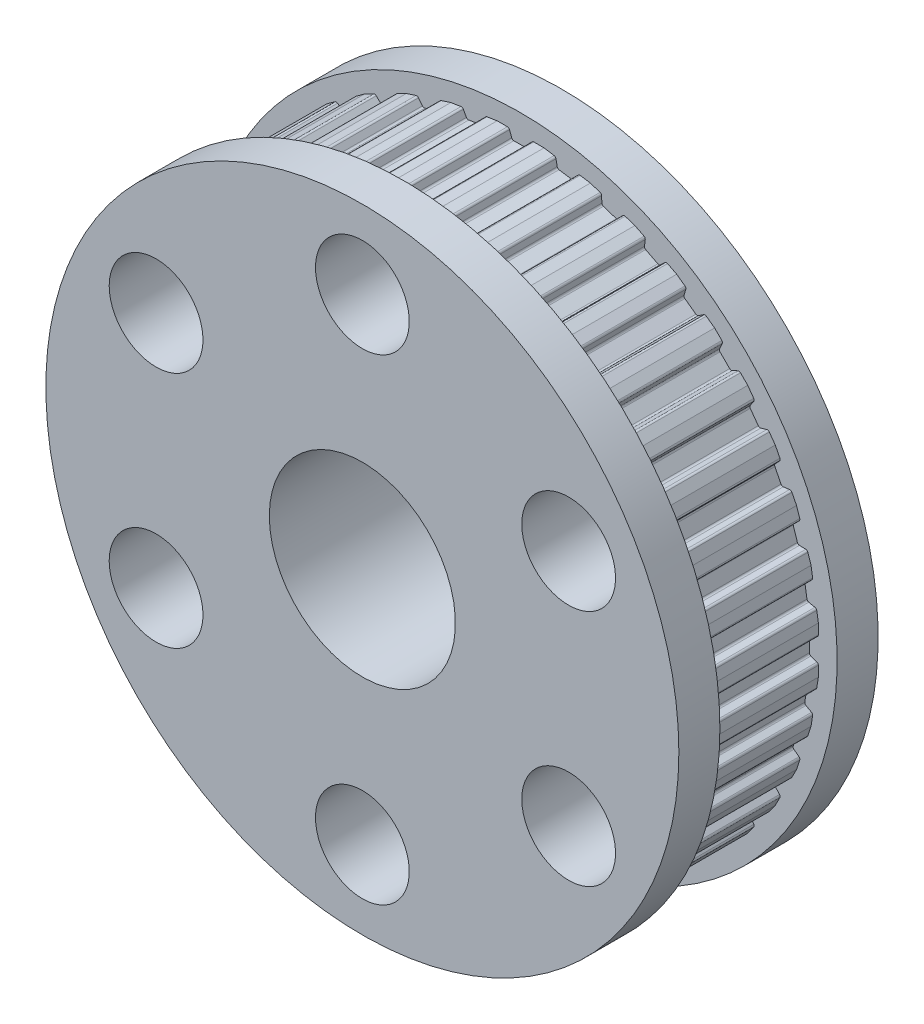
SolidWorks part; units mm, degrees
ref_plane "Front Plane" through (0, 0, 0) normal (0, 0, 1) x (1, 0, 0)
ref_plane "Top Plane" through (0, 0, 0) normal (0, 1, 0) x (1, 0, 0)
ref_plane "Right Plane" through (0, 0, 0) normal (1, 0, 0) x (0, 0, -1)
sketch "Sketch1" plane through (0, 0, 0) normal (0, 0, 1) x (1, 0, 0)
  line L0 (-50.7835, 0) -> (-50.3466, 0)
  line L5 (-50.2571, 0.0627) -> (-50.1641, 0.3183)
  line L6 (-50.0746, 0.381) -> (-49.4934, 0.381)
  line L7 (-49.784, 0.381) -> (-49.784, 0) construction
  line L8 (-49.3109, 0.0627) -> (-49.4039, 0.3183)
  line L39 (-51.2936, 0.1442) -> (-51.3455, 0.4113)
  line L40 (-50.2571, 0.0627) -> (-49.3109, 0.0627) construction
  line L56 (-49.2214, 0) -> (-48.7845, 0)
  line L60 (-51.9981, 0.5781) -> (-51.4241, 0.4872)
  line L61 (-52.2282, 0.2923) -> (-52.0963, 0.5302)
  line L62 (-52.7579, 0.3127) -> (-52.3264, 0.2444)
  line L63 (-51.215, 0.0683) -> (-50.7835, 0)
  line L64 (-53.2392, 0.535) -> (-53.2487, 0.8069)
  line L65 (-53.8671, 1.0737) -> (-53.3144, 0.8941)
  line L66 (-54.1391, 0.8274) -> (-53.9716, 1.0418)
  line L67 (-54.6591, 0.9304) -> (-54.2436, 0.7954)
  line L68 (-53.1734, 0.4477) -> (-52.7579, 0.3127)
  line L69 (-55.0997, 1.2253) -> (-55.0665, 1.4953)
  line L70 (-55.6356, 1.8556) -> (-55.1178, 1.5918)
  line L71 (-55.9428, 1.6549) -> (-55.7438, 1.8404)
  line L72 (-56.4403, 1.838) -> (-56.051, 1.6396)
  line L73 (-55.0484, 1.1288) -> (-54.6591, 0.9304)
  line L74 (-56.8293, 2.1981) -> (-56.7543, 2.4596)
  line L75 (-57.26, 2.9045) -> (-56.7898, 2.5629)
  line L76 (-57.5948, 2.7543) -> (-57.3693, 2.9064)
  line L77 (-58.0575, 3.013) -> (-57.7041, 2.7562)
  line L78 (-56.7937, 2.0948) -> (-56.4403, 1.838)
  line L79 (-58.3854, 3.4295) -> (-58.2704, 3.6761)
  line L80 (-58.7003, 4.1946) -> (-58.2894, 3.7837)
  line L81 (-59.0545, 4.0986) -> (-58.8079, 4.2136)
  line L82 (-59.471, 4.4265) -> (-59.1621, 4.1176)
  line L83 (-58.3664, 3.3219) -> (-58.0575, 3.013)
  line L84 (-59.7297, 4.8892) -> (-59.5776, 5.1147)
  line L85 (-59.9211, 5.6942) -> (-59.5795, 5.224)
  line L86 (-60.2859, 5.6547) -> (-60.0244, 5.7297)
  line L87 (-60.646, 6.0437) -> (-60.3892, 5.6903)
  line L88 (-59.7278, 4.7799) -> (-59.471, 4.4265)
  line L89 (-60.8291, 6.5412) -> (-60.6436, 6.7402)
  line L90 (-60.8922, 7.3662) -> (-60.6284, 6.8484)
  line L91 (-61.2587, 7.3843) -> (-60.9887, 7.4175)
  line L92 (-61.5536, 7.8249) -> (-61.3552, 7.4356)
  line L93 (-60.8444, 6.433) -> (-60.646, 6.0437)
  line L94 (-61.6566, 8.3449) -> (-61.4422, 8.5124)
  line L95 (-61.5899, 9.1696) -> (-61.4103, 8.6169)
  line L96 (-61.949, 9.2448) -> (-61.6771, 9.2353)
  line L97 (-62.1713, 9.7261) -> (-62.0363, 9.3106)
  line L98 (-61.6886, 8.2404) -> (-61.5536, 7.8249)
  line L99 (-62.1917, 10.2558) -> (-61.9538, 10.3877)
  line L100 (-61.9968, 11.0599) -> (-61.9059, 10.4859)
  line L101 (-62.3398, 11.1904) -> (-62.0727, 11.1385)
  line L102 (-62.484, 11.7005) -> (-62.4157, 11.269)
  line L103 (-62.2396, 10.1576) -> (-62.1713, 9.7261)
  line L104 (-62.4213, 12.2269) -> (-62.1657, 12.3199)
  line L105 (-62.103, 12.9906) -> (-62.103, 12.4094)
  line L106 (-62.4213, 13.1731) -> (-62.1657, 13.0801)
  line L107 (-62.484, 13.6995) -> (-62.484, 13.2626)
  line L108 (-62.484, 12.1374) -> (-62.484, 11.7005)
  line L109 (-62.3398, 14.2096) -> (-62.0727, 14.2615)
  line L110 (-61.9059, 14.9141) -> (-61.9968, 14.3401)
  line L111 (-62.1917, 15.1442) -> (-61.9538, 15.0123)
  line L112 (-62.1713, 15.6739) -> (-62.2396, 15.2424)
  line L113 (-62.4157, 14.131) -> (-62.484, 13.6995)
  line L114 (-61.949, 16.1552) -> (-61.6771, 16.1647)
  line L115 (-61.4103, 16.7831) -> (-61.5899, 16.2304)
  line L116 (-61.6566, 17.0551) -> (-61.4422, 16.8876)
  line L117 (-61.5536, 17.5751) -> (-61.6886, 17.1596)
  line L118 (-62.0363, 16.0894) -> (-62.1713, 15.6739)
  line L119 (-61.2587, 18.0157) -> (-60.9887, 17.9825)
  line L120 (-60.6284, 18.5516) -> (-60.8922, 18.0338)
  line L121 (-60.8291, 18.8588) -> (-60.6436, 18.6598)
  line L122 (-60.646, 19.3563) -> (-60.8444, 18.967)
  line L123 (-61.3552, 17.9644) -> (-61.5536, 17.5751)
  line L124 (-60.2859, 19.7453) -> (-60.0244, 19.6703)
  line L125 (-59.5795, 20.176) -> (-59.9211, 19.7058)
  line L126 (-59.7297, 20.5108) -> (-59.5776, 20.2853)
  line L127 (-59.471, 20.9735) -> (-59.7278, 20.6201)
  line L128 (-60.3892, 19.7097) -> (-60.646, 19.3563)
  line L129 (-59.0545, 21.3014) -> (-58.8079, 21.1864)
  line L130 (-58.2894, 21.6163) -> (-58.7003, 21.2054)
  line L131 (-58.3854, 21.9705) -> (-58.2704, 21.7239)
  line L132 (-58.0575, 22.387) -> (-58.3664, 22.0781)
  line L133 (-59.1621, 21.2824) -> (-59.471, 20.9735)
  line L134 (-57.5948, 22.6457) -> (-57.3693, 22.4936)
  line L135 (-56.7898, 22.8371) -> (-57.26, 22.4955)
  line L136 (-56.8293, 23.2019) -> (-56.7543, 22.9404)
  line L137 (-56.4403, 23.562) -> (-56.7937, 23.3052)
  line L138 (-57.7041, 22.6438) -> (-58.0575, 22.387)
  line L139 (-55.9428, 23.7451) -> (-55.7438, 23.5596)
  line L140 (-55.1178, 23.8082) -> (-55.6356, 23.5444)
  line L141 (-55.0997, 24.1747) -> (-55.0665, 23.9047)
  line L142 (-54.6591, 24.4696) -> (-55.0484, 24.2712)
  line L143 (-56.051, 23.7604) -> (-56.4403, 23.562)
  line L144 (-54.1391, 24.5726) -> (-53.9716, 24.3582)
  line L145 (-53.3144, 24.5059) -> (-53.8671, 24.3263)
  line L146 (-53.2392, 24.865) -> (-53.2487, 24.5931)
  line L147 (-52.7579, 25.0873) -> (-53.1734, 24.9523)
  line L148 (-54.2436, 24.6046) -> (-54.6591, 24.4696)
  line L149 (-52.2282, 25.1077) -> (-52.0963, 24.8698)
  line L150 (-51.4241, 24.9128) -> (-51.9981, 24.8219)
  line L151 (-51.2936, 25.2558) -> (-51.3455, 24.9887)
  line L152 (-50.7835, 25.4) -> (-51.215, 25.3317)
  line L153 (-52.3264, 25.1556) -> (-52.7579, 25.0873)
  line L154 (-50.2571, 25.3373) -> (-50.1641, 25.0817)
  line L155 (-49.4934, 25.019) -> (-50.0746, 25.019)
  line L156 (-49.3109, 25.3373) -> (-49.4039, 25.0817)
  line L157 (-48.7845, 25.4) -> (-49.2214, 25.4)
  line L158 (-50.3466, 25.4) -> (-50.7835, 25.4)
  line L159 (-48.2744, 25.2558) -> (-48.2225, 24.9887)
  line L160 (-47.5699, 24.8219) -> (-48.1439, 24.9128)
  line L161 (-47.3398, 25.1077) -> (-47.4717, 24.8698)
  line L162 (-46.8101, 25.0873) -> (-47.2416, 25.1556)
  line L163 (-48.353, 25.3317) -> (-48.7845, 25.4)
  line L164 (-46.3288, 24.865) -> (-46.3193, 24.5931)
  line L165 (-45.7009, 24.3263) -> (-46.2536, 24.5059)
  line L166 (-45.4289, 24.5726) -> (-45.5964, 24.3582)
  line L167 (-44.9089, 24.4696) -> (-45.3244, 24.6046)
  line L168 (-46.3946, 24.9523) -> (-46.8101, 25.0873)
  line L169 (-44.4683, 24.1747) -> (-44.5015, 23.9047)
  line L170 (-43.9324, 23.5444) -> (-44.4502, 23.8082)
  line L171 (-43.6252, 23.7451) -> (-43.8242, 23.5596)
  line L172 (-43.1277, 23.562) -> (-43.517, 23.7604)
  line L173 (-44.5196, 24.2712) -> (-44.9089, 24.4696)
  line L174 (-42.7387, 23.2019) -> (-42.8137, 22.9404)
  line L175 (-42.308, 22.4955) -> (-42.7782, 22.8371)
  line L176 (-41.9732, 22.6457) -> (-42.1987, 22.4936)
  line L177 (-41.5105, 22.387) -> (-41.8639, 22.6438)
  line L178 (-42.7743, 23.3052) -> (-43.1277, 23.562)
  line L179 (-41.1826, 21.9705) -> (-41.2976, 21.7239)
  line L180 (-40.8677, 21.2054) -> (-41.2786, 21.6163)
  line L181 (-40.5135, 21.3014) -> (-40.7601, 21.1864)
  line L182 (-40.097, 20.9735) -> (-40.4059, 21.2824)
  line L183 (-41.2016, 22.0781) -> (-41.5105, 22.387)
  line L184 (-39.8383, 20.5108) -> (-39.9904, 20.2853)
  line L185 (-39.6469, 19.7058) -> (-39.9885, 20.176)
  line L186 (-39.2821, 19.7453) -> (-39.5436, 19.6703)
  line L187 (-38.922, 19.3563) -> (-39.1788, 19.7097)
  line L188 (-39.8402, 20.6201) -> (-40.097, 20.9735)
  line L189 (-38.7389, 18.8588) -> (-38.9244, 18.6598)
  line L190 (-38.6758, 18.0338) -> (-38.9396, 18.5516)
  line L191 (-38.3093, 18.0157) -> (-38.5793, 17.9825)
  line L192 (-38.0144, 17.5751) -> (-38.2128, 17.9644)
  line L193 (-38.7236, 18.967) -> (-38.922, 19.3563)
  line L194 (-37.9114, 17.0551) -> (-38.1258, 16.8876)
  line L195 (-37.9781, 16.2304) -> (-38.1577, 16.7831)
  line L196 (-37.619, 16.1552) -> (-37.8909, 16.1647)
  line L197 (-37.3967, 15.6739) -> (-37.5317, 16.0894)
  line L198 (-37.8794, 17.1596) -> (-38.0144, 17.5751)
  line L199 (-37.3763, 15.1442) -> (-37.6142, 15.0123)
  line L200 (-37.5712, 14.3401) -> (-37.6621, 14.9141)
  line L201 (-37.2282, 14.2096) -> (-37.4953, 14.2615)
  line L202 (-37.084, 13.6995) -> (-37.1523, 14.131)
  line L203 (-37.3284, 15.2424) -> (-37.3967, 15.6739)
  line L204 (-37.1467, 13.1731) -> (-37.4023, 13.0801)
  line L205 (-37.465, 12.4094) -> (-37.465, 12.9906)
  line L206 (-37.1467, 12.2269) -> (-37.4023, 12.3199)
  line L207 (-37.084, 11.7005) -> (-37.084, 12.1374)
  line L208 (-37.084, 13.2626) -> (-37.084, 13.6995)
  line L209 (-37.2282, 11.1904) -> (-37.4953, 11.1385)
  line L210 (-37.6621, 10.4859) -> (-37.5712, 11.0599)
  line L211 (-37.3763, 10.2558) -> (-37.6142, 10.3877)
  line L212 (-37.3967, 9.7261) -> (-37.3284, 10.1576)
  line L213 (-37.1523, 11.269) -> (-37.084, 11.7005)
  line L214 (-37.619, 9.2448) -> (-37.8909, 9.2353)
  line L215 (-38.1577, 8.6169) -> (-37.9781, 9.1696)
  line L216 (-37.9114, 8.3449) -> (-38.1258, 8.5124)
  line L217 (-38.0144, 7.8249) -> (-37.8794, 8.2404)
  line L218 (-37.5317, 9.3106) -> (-37.3967, 9.7261)
  line L219 (-38.3093, 7.3843) -> (-38.5793, 7.4175)
  line L220 (-38.9396, 6.8484) -> (-38.6758, 7.3662)
  line L221 (-38.7389, 6.5412) -> (-38.9244, 6.7402)
  line L222 (-38.922, 6.0437) -> (-38.7236, 6.433)
  line L223 (-38.2128, 7.4356) -> (-38.0144, 7.8249)
  line L224 (-39.2821, 5.6547) -> (-39.5436, 5.7297)
  line L225 (-39.9885, 5.224) -> (-39.6469, 5.6942)
  line L226 (-39.8383, 4.8892) -> (-39.9904, 5.1147)
  line L227 (-40.097, 4.4265) -> (-39.8402, 4.7799)
  line L228 (-39.1788, 5.6903) -> (-38.922, 6.0437)
  line L229 (-40.5135, 4.0986) -> (-40.7601, 4.2136)
  line L230 (-41.2786, 3.7837) -> (-40.8677, 4.1946)
  line L231 (-41.1826, 3.4295) -> (-41.2976, 3.6761)
  line L232 (-41.5105, 3.013) -> (-41.2016, 3.3219)
  line L233 (-40.4059, 4.1176) -> (-40.097, 4.4265)
  line L234 (-41.9732, 2.7543) -> (-42.1987, 2.9064)
  line L235 (-42.7782, 2.5629) -> (-42.308, 2.9045)
  line L236 (-42.7387, 2.1981) -> (-42.8137, 2.4596)
  line L237 (-43.1277, 1.838) -> (-42.7743, 2.0948)
  line L238 (-41.8639, 2.7562) -> (-41.5105, 3.013)
  line L239 (-43.6252, 1.6549) -> (-43.8242, 1.8404)
  line L240 (-44.4502, 1.5918) -> (-43.9324, 1.8556)
  line L241 (-44.4683, 1.2253) -> (-44.5015, 1.4953)
  line L242 (-44.9089, 0.9304) -> (-44.5196, 1.1288)
  line L243 (-43.517, 1.6396) -> (-43.1277, 1.838)
  line L244 (-45.4289, 0.8274) -> (-45.5964, 1.0418)
  line L245 (-46.2536, 0.8941) -> (-45.7009, 1.0737)
  line L246 (-46.3288, 0.535) -> (-46.3193, 0.8069)
  line L247 (-46.8101, 0.3127) -> (-46.3946, 0.4477)
  line L248 (-45.3244, 0.7954) -> (-44.9089, 0.9304)
  line L249 (-47.3398, 0.2923) -> (-47.4717, 0.5302)
  line L250 (-48.1439, 0.4872) -> (-47.5699, 0.5781)
  line L251 (-48.2744, 0.1442) -> (-48.2225, 0.4113)
  line L252 (-48.7845, 0) -> (-48.353, 0.0683)
  line L253 (-47.2416, 0.2444) -> (-46.8101, 0.3127)
  arc A0 (-50.3466, 0) -> (-50.2571, 0.0627) centre (-50.3466, 0.0952) ccw
  arc A1 (-50.1641, 0.3183) -> (-50.0746, 0.381) centre (-50.0746, 0.2857) cw
  arc A2 (-49.4039, 0.3183) -> (-49.4934, 0.381) centre (-49.4934, 0.2857) ccw
  arc A3 (-49.2214, 0) -> (-49.3109, 0.0627) centre (-49.2214, 0.0952) cw
  arc A4 (-51.215, 0.0683) -> (-51.2936, 0.1442) centre (-51.2001, 0.1624) cw
  arc A5 (-51.3455, 0.4113) -> (-51.4241, 0.4872) centre (-51.439, 0.3931) ccw
  arc A6 (-52.0963, 0.5302) -> (-51.9981, 0.5781) centre (-52.013, 0.484) cw
  arc A7 (-52.3264, 0.2444) -> (-52.2282, 0.2923) centre (-52.3115, 0.3385) ccw
  arc A8 (-53.1734, 0.4477) -> (-53.2392, 0.535) centre (-53.144, 0.5383) cw
  arc A9 (-53.2487, 0.8069) -> (-53.3144, 0.8941) centre (-53.3439, 0.8036) ccw
  arc A10 (-53.9716, 1.0418) -> (-53.8671, 1.0737) centre (-53.8966, 0.9831) cw
  arc A11 (-54.2436, 0.7954) -> (-54.1391, 0.8274) centre (-54.2142, 0.886) ccw
  arc A12 (-55.0484, 1.1288) -> (-55.0997, 1.2253) centre (-55.0051, 1.2137) cw
  arc A13 (-55.0665, 1.4953) -> (-55.1178, 1.5918) centre (-55.1611, 1.5069) ccw
  arc A14 (-55.7438, 1.8404) -> (-55.6356, 1.8556) centre (-55.6789, 1.7707) cw
  arc A15 (-56.051, 1.6396) -> (-55.9428, 1.6549) centre (-56.0077, 1.7245) ccw
  arc A16 (-56.7937, 2.0948) -> (-56.8293, 2.1981) centre (-56.7377, 2.1718) cw
  arc A17 (-56.7543, 2.4596) -> (-56.7898, 2.5629) centre (-56.8458, 2.4859) ccw
  arc A18 (-57.3693, 2.9064) -> (-57.26, 2.9045) centre (-57.316, 2.8275) cw
  arc A19 (-57.7041, 2.7562) -> (-57.5948, 2.7543) centre (-57.6481, 2.8333) ccw
  arc A20 (-58.3664, 3.3219) -> (-58.3854, 3.4295) centre (-58.2991, 3.3893) cw
  arc A21 (-58.2704, 3.6761) -> (-58.2894, 3.7837) centre (-58.3567, 3.7163) ccw
  arc A22 (-58.8079, 4.2136) -> (-58.7003, 4.1946) centre (-58.7677, 4.1273) cw
  arc A23 (-59.1621, 4.1176) -> (-59.0545, 4.0986) centre (-59.0947, 4.1849) ccw
  arc A24 (-59.7278, 4.7799) -> (-59.7297, 4.8892) centre (-59.6507, 4.8359) cw
  arc A25 (-59.5776, 5.1147) -> (-59.5795, 5.224) centre (-59.6565, 5.168) ccw
  arc A26 (-60.0244, 5.7297) -> (-59.9211, 5.6942) centre (-59.9981, 5.6382) cw
  arc A27 (-60.3892, 5.6903) -> (-60.2859, 5.6547) centre (-60.3122, 5.7463) ccw
  arc A28 (-60.8444, 6.433) -> (-60.8291, 6.5412) centre (-60.7595, 6.4763) cw
  arc A29 (-60.6436, 6.7402) -> (-60.6284, 6.8484) centre (-60.7133, 6.8051) ccw
  arc A30 (-60.9887, 7.4175) -> (-60.8922, 7.3662) centre (-60.9771, 7.3229) cw
  arc A31 (-61.3552, 7.4356) -> (-61.2587, 7.3843) centre (-61.2703, 7.4789) ccw
  arc A32 (-61.6886, 8.2404) -> (-61.6566, 8.3449) centre (-61.598, 8.2698) cw
  arc A33 (-61.4422, 8.5124) -> (-61.4103, 8.6169) centre (-61.5009, 8.5874) ccw
  arc A34 (-61.6771, 9.2353) -> (-61.5899, 9.1696) centre (-61.6804, 9.1401) cw
  arc A35 (-62.0363, 9.3106) -> (-61.949, 9.2448) centre (-61.9457, 9.34) ccw
  arc A36 (-62.2396, 10.1576) -> (-62.1917, 10.2558) centre (-62.1455, 10.1725) cw
  arc A37 (-61.9538, 10.3877) -> (-61.9059, 10.4859) centre (-62, 10.471) ccw
  arc A38 (-62.0727, 11.1385) -> (-61.9968, 11.0599) centre (-62.0909, 11.045) cw
  arc A39 (-62.4157, 11.269) -> (-62.3398, 11.1904) centre (-62.3216, 11.2839) ccw
  arc A40 (-62.484, 12.1374) -> (-62.4213, 12.2269) centre (-62.3888, 12.1374) cw
  arc A41 (-62.1657, 12.3199) -> (-62.103, 12.4094) centre (-62.1983, 12.4094) ccw
  arc A42 (-62.1657, 13.0801) -> (-62.103, 12.9906) centre (-62.1983, 12.9906) cw
  arc A43 (-62.484, 13.2626) -> (-62.4213, 13.1731) centre (-62.3888, 13.2626) ccw
  arc A44 (-62.4157, 14.131) -> (-62.3398, 14.2096) centre (-62.3216, 14.1161) cw
  arc A45 (-62.0727, 14.2615) -> (-61.9968, 14.3401) centre (-62.0909, 14.355) ccw
  arc A46 (-61.9538, 15.0123) -> (-61.9059, 14.9141) centre (-62, 14.929) cw
  arc A47 (-62.2396, 15.2424) -> (-62.1917, 15.1442) centre (-62.1455, 15.2275) ccw
  arc A48 (-62.0363, 16.0894) -> (-61.949, 16.1552) centre (-61.9457, 16.06) cw
  arc A49 (-61.6771, 16.1647) -> (-61.5899, 16.2304) centre (-61.6804, 16.2599) ccw
  arc A50 (-61.4422, 16.8876) -> (-61.4103, 16.7831) centre (-61.5009, 16.8126) cw
  arc A51 (-61.6886, 17.1596) -> (-61.6566, 17.0551) centre (-61.598, 17.1302) ccw
  arc A52 (-61.3552, 17.9644) -> (-61.2587, 18.0157) centre (-61.2703, 17.9211) cw
  arc A53 (-60.9887, 17.9825) -> (-60.8922, 18.0338) centre (-60.9771, 18.0771) ccw
  arc A54 (-60.6436, 18.6598) -> (-60.6284, 18.5516) centre (-60.7133, 18.5949) cw
  arc A55 (-60.8444, 18.967) -> (-60.8291, 18.8588) centre (-60.7595, 18.9237) ccw
  arc A56 (-60.3892, 19.7097) -> (-60.2859, 19.7453) centre (-60.3122, 19.6537) cw
  arc A57 (-60.0244, 19.6703) -> (-59.9211, 19.7058) centre (-59.9981, 19.7618) ccw
  arc A58 (-59.5776, 20.2853) -> (-59.5795, 20.176) centre (-59.6565, 20.232) cw
  arc A59 (-59.7278, 20.6201) -> (-59.7297, 20.5108) centre (-59.6507, 20.5641) ccw
  arc A60 (-59.1621, 21.2824) -> (-59.0545, 21.3014) centre (-59.0947, 21.2151) cw
  arc A61 (-58.8079, 21.1864) -> (-58.7003, 21.2054) centre (-58.7677, 21.2727) ccw
  arc A62 (-58.2704, 21.7239) -> (-58.2894, 21.6163) centre (-58.3567, 21.6837) cw
  arc A63 (-58.3664, 22.0781) -> (-58.3854, 21.9705) centre (-58.2991, 22.0107) ccw
  arc A64 (-57.7041, 22.6438) -> (-57.5948, 22.6457) centre (-57.6481, 22.5667) cw
  arc A65 (-57.3693, 22.4936) -> (-57.26, 22.4955) centre (-57.316, 22.5725) ccw
  arc A66 (-56.7543, 22.9404) -> (-56.7898, 22.8371) centre (-56.8458, 22.9141) cw
  arc A67 (-56.7937, 23.3052) -> (-56.8293, 23.2019) centre (-56.7377, 23.2282) ccw
  arc A68 (-56.051, 23.7604) -> (-55.9428, 23.7451) centre (-56.0077, 23.6755) cw
  arc A69 (-55.7438, 23.5596) -> (-55.6356, 23.5444) centre (-55.6789, 23.6293) ccw
  arc A70 (-55.0665, 23.9047) -> (-55.1178, 23.8082) centre (-55.1611, 23.8931) cw
  arc A71 (-55.0484, 24.2712) -> (-55.0997, 24.1747) centre (-55.0051, 24.1863) ccw
  arc A72 (-54.2436, 24.6046) -> (-54.1391, 24.5726) centre (-54.2142, 24.514) cw
  arc A73 (-53.9716, 24.3582) -> (-53.8671, 24.3263) centre (-53.8966, 24.4169) ccw
  arc A74 (-53.2487, 24.5931) -> (-53.3144, 24.5059) centre (-53.3439, 24.5964) cw
  arc A75 (-53.1734, 24.9523) -> (-53.2392, 24.865) centre (-53.144, 24.8617) ccw
  arc A76 (-52.3264, 25.1556) -> (-52.2282, 25.1077) centre (-52.3115, 25.0615) cw
  arc A77 (-52.0963, 24.8698) -> (-51.9981, 24.8219) centre (-52.013, 24.916) ccw
  arc A78 (-51.3455, 24.9887) -> (-51.4241, 24.9128) centre (-51.439, 25.0069) cw
  arc A79 (-51.215, 25.3317) -> (-51.2936, 25.2558) centre (-51.2001, 25.2376) ccw
  arc A80 (-50.3466, 25.4) -> (-50.2571, 25.3373) centre (-50.3466, 25.3048) cw
  arc A81 (-50.1641, 25.0817) -> (-50.0746, 25.019) centre (-50.0746, 25.1143) ccw
  arc A82 (-49.4039, 25.0817) -> (-49.4934, 25.019) centre (-49.4934, 25.1143) cw
  arc A83 (-49.2214, 25.4) -> (-49.3109, 25.3373) centre (-49.2214, 25.3048) ccw
  arc A84 (-48.353, 25.3317) -> (-48.2744, 25.2558) centre (-48.3679, 25.2376) cw
  arc A85 (-48.2225, 24.9887) -> (-48.1439, 24.9128) centre (-48.129, 25.0069) ccw
  arc A86 (-47.4717, 24.8698) -> (-47.5699, 24.8219) centre (-47.555, 24.916) cw
  arc A87 (-47.2416, 25.1556) -> (-47.3398, 25.1077) centre (-47.2565, 25.0615) ccw
  arc A88 (-46.3946, 24.9523) -> (-46.3288, 24.865) centre (-46.424, 24.8617) cw
  arc A89 (-46.3193, 24.5931) -> (-46.2536, 24.5059) centre (-46.2241, 24.5964) ccw
  arc A90 (-45.5964, 24.3582) -> (-45.7009, 24.3263) centre (-45.6714, 24.4169) cw
  arc A91 (-45.3244, 24.6046) -> (-45.4289, 24.5726) centre (-45.3538, 24.514) ccw
  arc A92 (-44.5196, 24.2712) -> (-44.4683, 24.1747) centre (-44.5629, 24.1863) cw
  arc A93 (-44.5015, 23.9047) -> (-44.4502, 23.8082) centre (-44.4069, 23.8931) ccw
  arc A94 (-43.8242, 23.5596) -> (-43.9324, 23.5444) centre (-43.8891, 23.6293) cw
  arc A95 (-43.517, 23.7604) -> (-43.6252, 23.7451) centre (-43.5603, 23.6755) ccw
  arc A96 (-42.7743, 23.3052) -> (-42.7387, 23.2019) centre (-42.8303, 23.2282) cw
  arc A97 (-42.8137, 22.9404) -> (-42.7782, 22.8371) centre (-42.7222, 22.9141) ccw
  arc A98 (-42.1987, 22.4936) -> (-42.308, 22.4955) centre (-42.252, 22.5725) cw
  arc A99 (-41.8639, 22.6438) -> (-41.9732, 22.6457) centre (-41.9199, 22.5667) ccw
  arc A100 (-41.2016, 22.0781) -> (-41.1826, 21.9705) centre (-41.2689, 22.0107) cw
  arc A101 (-41.2976, 21.7239) -> (-41.2786, 21.6163) centre (-41.2113, 21.6837) ccw
  arc A102 (-40.7601, 21.1864) -> (-40.8677, 21.2054) centre (-40.8003, 21.2727) cw
  arc A103 (-40.4059, 21.2824) -> (-40.5135, 21.3014) centre (-40.4733, 21.2151) ccw
  arc A104 (-39.8402, 20.6201) -> (-39.8383, 20.5108) centre (-39.9173, 20.5641) cw
  arc A105 (-39.9904, 20.2853) -> (-39.9885, 20.176) centre (-39.9115, 20.232) ccw
  arc A106 (-39.5436, 19.6703) -> (-39.6469, 19.7058) centre (-39.5699, 19.7618) cw
  arc A107 (-39.1788, 19.7097) -> (-39.2821, 19.7453) centre (-39.2558, 19.6537) ccw
  arc A108 (-38.7236, 18.967) -> (-38.7389, 18.8588) centre (-38.8085, 18.9237) cw
  arc A109 (-38.9244, 18.6598) -> (-38.9396, 18.5516) centre (-38.8547, 18.5949) ccw
  arc A110 (-38.5793, 17.9825) -> (-38.6758, 18.0338) centre (-38.5909, 18.0771) cw
  arc A111 (-38.2128, 17.9644) -> (-38.3093, 18.0157) centre (-38.2977, 17.9211) ccw
  arc A112 (-37.8794, 17.1596) -> (-37.9114, 17.0551) centre (-37.97, 17.1302) cw
  arc A113 (-38.1258, 16.8876) -> (-38.1577, 16.7831) centre (-38.0671, 16.8126) ccw
  arc A114 (-37.8909, 16.1647) -> (-37.9781, 16.2304) centre (-37.8876, 16.2599) cw
  arc A115 (-37.5317, 16.0894) -> (-37.619, 16.1552) centre (-37.6223, 16.06) ccw
  arc A116 (-37.3284, 15.2424) -> (-37.3763, 15.1442) centre (-37.4225, 15.2275) cw
  arc A117 (-37.6142, 15.0123) -> (-37.6621, 14.9141) centre (-37.568, 14.929) ccw
  arc A118 (-37.4953, 14.2615) -> (-37.5712, 14.3401) centre (-37.4771, 14.355) cw
  arc A119 (-37.1523, 14.131) -> (-37.2282, 14.2096) centre (-37.2464, 14.1161) ccw
  arc A120 (-37.084, 13.2626) -> (-37.1467, 13.1731) centre (-37.1792, 13.2626) cw
  arc A121 (-37.4023, 13.0801) -> (-37.465, 12.9906) centre (-37.3697, 12.9906) ccw
  arc A122 (-37.4023, 12.3199) -> (-37.465, 12.4094) centre (-37.3698, 12.4094) cw
  arc A123 (-37.084, 12.1374) -> (-37.1467, 12.2269) centre (-37.1792, 12.1374) ccw
  arc A124 (-37.1523, 11.269) -> (-37.2282, 11.1904) centre (-37.2464, 11.2839) cw
  arc A125 (-37.4953, 11.1385) -> (-37.5712, 11.0599) centre (-37.4771, 11.045) ccw
  arc A126 (-37.6142, 10.3877) -> (-37.6621, 10.4859) centre (-37.568, 10.471) cw
  arc A127 (-37.3284, 10.1576) -> (-37.3763, 10.2558) centre (-37.4225, 10.1725) ccw
  arc A128 (-37.5317, 9.3106) -> (-37.619, 9.2448) centre (-37.6223, 9.34) cw
  arc A129 (-37.8909, 9.2353) -> (-37.9781, 9.1696) centre (-37.8876, 9.1401) ccw
  arc A130 (-38.1258, 8.5124) -> (-38.1577, 8.6169) centre (-38.0671, 8.5874) cw
  arc A131 (-37.8794, 8.2404) -> (-37.9114, 8.3449) centre (-37.97, 8.2698) ccw
  arc A132 (-38.2128, 7.4356) -> (-38.3093, 7.3843) centre (-38.2977, 7.4789) cw
  arc A133 (-38.5793, 7.4175) -> (-38.6758, 7.3662) centre (-38.5909, 7.3229) ccw
  arc A134 (-38.9244, 6.7402) -> (-38.9396, 6.8484) centre (-38.8547, 6.8051) cw
  arc A135 (-38.7236, 6.433) -> (-38.7389, 6.5412) centre (-38.8085, 6.4763) ccw
  arc A136 (-39.1788, 5.6903) -> (-39.2821, 5.6547) centre (-39.2558, 5.7463) cw
  arc A137 (-39.5436, 5.7297) -> (-39.6469, 5.6942) centre (-39.5699, 5.6382) ccw
  arc A138 (-39.9904, 5.1147) -> (-39.9885, 5.224) centre (-39.9115, 5.168) cw
  arc A139 (-39.8402, 4.7799) -> (-39.8383, 4.8892) centre (-39.9173, 4.8359) ccw
  arc A140 (-40.4059, 4.1176) -> (-40.5135, 4.0986) centre (-40.4733, 4.1849) cw
  arc A141 (-40.7601, 4.2136) -> (-40.8677, 4.1946) centre (-40.8003, 4.1273) ccw
  arc A142 (-41.2976, 3.6761) -> (-41.2786, 3.7837) centre (-41.2113, 3.7163) cw
  arc A143 (-41.2016, 3.3219) -> (-41.1826, 3.4295) centre (-41.2689, 3.3893) ccw
  arc A144 (-41.8639, 2.7562) -> (-41.9732, 2.7543) centre (-41.9199, 2.8333) cw
  arc A145 (-42.1987, 2.9064) -> (-42.308, 2.9045) centre (-42.252, 2.8275) ccw
  arc A146 (-42.8137, 2.4596) -> (-42.7782, 2.5629) centre (-42.7222, 2.4859) cw
  arc A147 (-42.7743, 2.0948) -> (-42.7387, 2.1981) centre (-42.8303, 2.1718) ccw
  arc A148 (-43.517, 1.6396) -> (-43.6252, 1.6549) centre (-43.5603, 1.7245) cw
  arc A149 (-43.8242, 1.8404) -> (-43.9324, 1.8556) centre (-43.8891, 1.7707) ccw
  arc A150 (-44.5015, 1.4953) -> (-44.4502, 1.5918) centre (-44.4069, 1.5069) cw
  arc A151 (-44.5196, 1.1288) -> (-44.4683, 1.2253) centre (-44.5629, 1.2137) ccw
  arc A152 (-45.3244, 0.7954) -> (-45.4289, 0.8274) centre (-45.3538, 0.886) cw
  arc A153 (-45.5964, 1.0418) -> (-45.7009, 1.0737) centre (-45.6714, 0.9831) ccw
  arc A154 (-46.3193, 0.8069) -> (-46.2536, 0.8941) centre (-46.2241, 0.8036) cw
  arc A155 (-46.3946, 0.4477) -> (-46.3288, 0.535) centre (-46.424, 0.5383) ccw
  arc A156 (-47.2416, 0.2444) -> (-47.3398, 0.2923) centre (-47.2565, 0.3385) cw
  arc A157 (-47.4717, 0.5302) -> (-47.5699, 0.5781) centre (-47.555, 0.484) ccw
  arc A158 (-48.2225, 0.4113) -> (-48.1439, 0.4872) centre (-48.129, 0.3931) cw
  arc A159 (-48.353, 0.0683) -> (-48.2744, 0.1442) centre (-48.3679, 0.1624) ccw
  point P1 (-50.292, 0.0172)
  point P2 (-49.784, 12.7)
  point P7 (-49.276, 0.0172)
  point P570 (-49.784, 12.7)
  dimension "D1" = 0.0953
  dimension "D2" = 40
  dimension "D3" = 40
  dimension "D4" = 1.016
  dimension "D7" = 0.381
sketch "Sketch2" plane through (0, 0, 0) normal (0, 0, 1) x (1, 0, 0)
  point P0 (-49.784, 12.7)
  point P1 (0, 0)
extrude "Boss-Extrude1" add sketch "Sketch1" along normal blind 5
sketch "Sketch3" plane through (0, 0, 5) normal (0, 0, 1) x (1, 0, 0)
  circle A0 centre (-49.784, 12.7) radius 13.5
extrude "Boss-Extrude2" add sketch "Sketch3" along normal blind 1.75
sketch "Sketch4" plane through (0, 0, 0) normal (0, 0, -1) x (-1, 0, 0)
  circle A0 centre (49.784, 12.7) radius 13.5
extrude "Boss-Extrude3" add sketch "Sketch4" along normal blind 1.75
sketch "Sketch6" plane through (0, 0, -1.75) normal (0, 0, -1) x (-1, 0, 0)
  point P0 (49.784, 12.7)
hole_wizard "5/16 (0.3125) Dowel Hole2" positions "Sketch6" profile "Sketch7" hole size "5/16" standard "ANSI Inch" end condition through all
sketch "Sketch7" plane through (-49.784, 12.7, -1.75) normal (1, 0, 0) x (0, 1, 0)
  line L0 (0, 0) -> (0, 8.5)
  line L1 (0, 8.5) -> (3.9687, 8.5)
  line L2 (3.9687, 8.5) -> (3.9687, 0)
  line L5 (3.9687, 0) -> (0, 0)
  line L11 (0, -6.35) -> (0, 107.95) construction
  dimension "Thru Hole Dia." = 7.9375
  dimension "Thru Hole Depth" = 8.5
sketch "Sketch8" plane through (0, 0, -1.75) normal (0, 0, -1) x (-1, 0, 0)
  point P0 (49.784, 2.54)
  point P1 (49.784, 12.7)
  point P5 (49.784, 12.7)
  dimension "D1" = 10.16
hole_wizard "Ø4.0mm Dowel Hole1" positions "Sketch8" profile "Sketch9" hole size "Ø4.0" standard "ANSI Metric" end condition through all
sketch "Sketch9" plane through (-49.784, 2.54, -1.75) normal (1, 0, 0) x (0, 1, 0)
  line L0 (0, 0) -> (0, 8.5)
  line L1 (0, 8.5) -> (2, 8.5)
  line L2 (2, 8.5) -> (2, 0)
  line L5 (2, 0) -> (0, 0)
  line L11 (0, -6.35) -> (0, 107.95) construction
  dimension "Thru Hole Dia." = 4
  dimension "Thru Hole Depth" = 8.5
sketch "Sketch10" plane through (0, 0, 0) normal (1, 0, 0) x (0, 0, -1)
  line L0 (1.75, 12.7) -> (-6.75, 12.7)
  line L1 (1.75, -0.8) -> (1.75, 26.2) construction
  line L2 (-6.75, 26.2) -> (-6.75, -0.8) construction
ref_axis "Axis1" through (-49.784, 12.7, 6.75) along (0, 0, -1)
pattern_circular "CirPattern1" count 6 over 360 about axis through (-49.784, 12.7, 6.75) along (0, 0, -1) of "Ø4.0mm Dowel Hole1"
